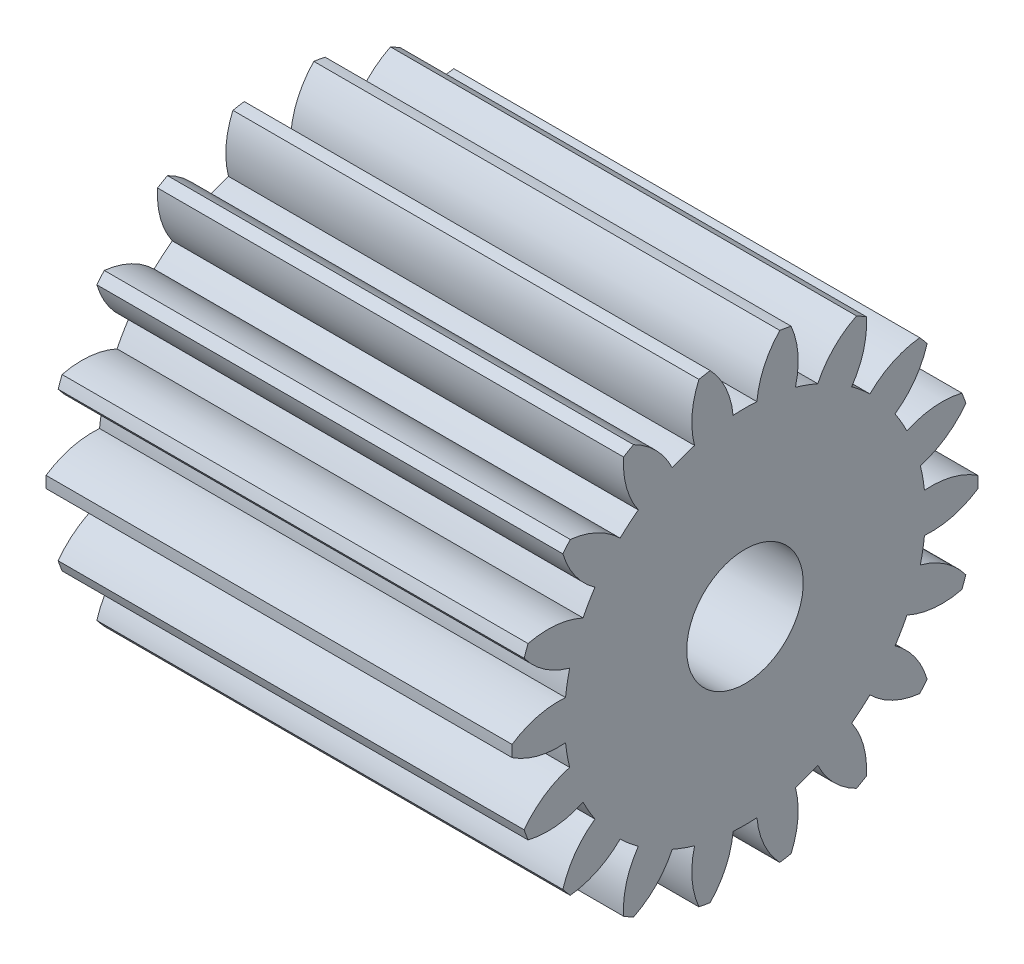
SolidWorks part; units mm, degrees
ref_plane "Plane1" through (0, 0, 0) normal (0, 0, 1) x (1, 0, 0)
ref_plane "Plane2" through (0, 0, 0) normal (0, 1, 0) x (1, 0, 0)
ref_plane "Plane3" through (0, 0, 0) normal (1, 0, 0) x (0, 0, -1)
sketch "HoldingSke" plane through (0, 0, 0) normal (0, 1, 0) x (1, 0, 0)
  line L0 (0, 0) -> (1.9021, -0.618)
  line L1 (-15, 0) -> (100, 0) construction
  line L2 (0, 0) -> (-2.1039, 2.3779)
  line L3 (0, 0) -> (-11.863, 4.5341)
  line L4 (0, 0) -> (8.2133, 2.6687)
  line L5 (0, 0) -> (-46.8476, -17.4728)
  line L6 (0, 0) -> (-8.2896, -5.593)
  line L7 (-2.1039, 2.3779) -> (8.6586, 51.2059)
  line L8 (-76.2, 54.61) -> (-76.1, 54.61)
  line L9 (-71.009, 38.7566) -> (-53.1078, 45.2721)
  line L10 (-76.2, 71.12) -> (104.1128, 71.12)
  line L11 (0, 0) -> (-10, 0)
  line L12 (-76.2, 101.6) -> (-76.181, 101.6)
  line L13 (24.9733, 27.94) -> (52.9518, 28.4284)
  line L14 (24.9733, 27.94) -> (24.9743, 27.94)
  line L15 (24.9733, 27.94) -> (100.4006, 29.5858)
  line L16 (-63.627, -0.5) -> (-12.827, -0.5)
  circle A0 centre (0, 0) radius 0.4
  circle A1 centre (0, 0) radius 3.874
  circle A2 centre (0, 0) radius 37.5
  circle A3 centre (0, 0) radius 1.25
  dimension "Num_teeth" = 18
  dimension "Pitch_radius" = 180.3128
  dimension "Width" = 10
  dimension "Thickness" = 10
sketch "BasProSke" plane through (0, 0, 0) normal (0, 1, 0) x (1, 0, 0)
  line L0 (-10, 0) -> (60, 0) construction
  line L1 (0, 0) -> (0, 5)
  line L2 (0, 0) -> (10, 0)
  line L3 (10, 0) -> (10, 5)
  line L4 (10, 5) -> (0, 5)
  dimension "Thickness" = 10
  dimension "Diameter" = 10
revolve "Base-Revolve" add sketch "BasProSke" angle 360 about L0
sketch "TooCutSke" plane through (0, 0, 0) normal (1, 0, 0) x (0, 0, -1)
  line L1 (0, 0) -> (0, 107) construction
  line L2 (0, 0) -> (-0.4254, 4.4798) construction
  line L3 (0, 0) -> (-1.5579, 8.835) construction
  line L4 (-0.4254, 4.4798) -> (-0.7789, 4.4175) construction
  arc A0 (0.2553, 3.8656) -> (-0.2553, 3.8656) centre (0, 0) ccw
  arc A1 (0.7686, 4.9663) -> (-0.7686, 4.9663) centre (0, 0) ccw
  circle A2 centre (0, 0) radius 4.5 construction
  circle A3 centre (0, 0) radius 4.2286 construction
  arc A4 (-0.2553, 3.8656) -> (-0.7686, 4.9663) centre (-2.0476, 3.6998) ccw
  arc A5 (0.7686, 4.9663) -> (0.2553, 3.8656) centre (2.0476, 3.6998) ccw
extrude "ToothCut" cut sketch "TooCutSke" along normal through all
fillet "Breaks" [suppressed] radius 0.01 tangent propagation no
fillet "RootFillets" [suppressed] radius 0.126
pattern_circular "TeethCuts" count 18 every 20 about axis through (-10, 0, 0) along (1, 0, 0) of "ToothCut", "RootFillets", "Breaks"
sketch "HubNeaOneSke" plane through (0, 0, 0) normal (-1, 0, 0) x (0, 0, 1)
  circle A0 centre (0, 0) radius 3.874
  dimension "Diameter" = 7.748
extrude "HubNearOne" [suppressed] add sketch "HubNeaOneSke" along normal blind 40.0001
sketch "HubNeaBotSke" plane through (0, 0, 0) normal (-1, 0, 0) x (0, 0, 1)
  circle A0 centre (0, 0) radius 3.874
  dimension "Diameter" = 7.748
extrude "HubNearBoth" [suppressed] add sketch "HubNeaBotSke" along normal blind 20
ref_plane "FarPln" through (10, 0, 0) normal (1, 0, 0) x (0, 0, -1)
sketch "HubFarSke" plane through (10, 0, 0) normal (1, 0, 0) x (0, 0, -1)
  circle A0 centre (0, 0) radius 3.874
  dimension "Diameter" = 7.748
extrude "HubFar" [suppressed] add sketch "HubFarSke" along normal blind 20
sketch "BorSke" plane through (0, 0, 0) normal (1, 0, 0) x (0, 0, -1)
  circle A0 centre (0, 0) radius 1.25
  dimension "Diameter" = 2.5
extrude "Bore" cut sketch "BorSke" along normal mid plane 100.0001
sketch "KeySke" plane through (0, 0, 0) normal (1, 0, 0) x (0, 0, -1)
  line L0 (-0.05, 0) -> (-0.05, 1.35)
  line L1 (-0.05, 1.35) -> (0.05, 1.35)
  line L2 (0.05, 1.35) -> (0.05, 0)
  line L3 (0, 0) -> (0, 34) construction
  line L4 (-0.05, 0) -> (0.05, 0)
  dimension "Width" = 0.1
extrude "Keyway" [suppressed] cut sketch "KeySke" along normal mid plane 100.0001
pattern_circular "Keyway2" [suppressed] count 2 every 90 about axis through (-10, 0, 0) along (1, 0, 0)
equation "' \"Module@HoldingSke\" = 6.35"
equation "' \"Num_teeth@HoldingSke\" = 12"
equation "' \"Ap@HoldingSke\" =  20"
equation "' \"Ap@HoldingSke\" = 20"
equation "' \"Width@HoldingSke\" = 0.5 * 25.4"
equation "' \"Hub_dia@HoldingSke\"= 1 * 25.4"
equation "' \"Hub_dia@HoldingSke\" = 1 * 25.4"
equation "' \"Overall_len@HoldingSke\" = 1.0 * 25.4"
equation "' \"Bore@HoldingSke\" = 0.75 * 25.4"
equation "' \"T_dim@HoldingSke\" = 0.1 * 25.4"
equation "' \"Width@KeySke\" = 0.25 * 25.4"
equation "' \"Show_teeth@HoldingSke\" = 13"
equation "' \"Backlash@HoldingSke\" = 0.009 * 25.4"
equation "' \"Addendum_fac@HoldingSke\" = 1.0"
equation "' \"Dedendum_fac@HoldingSke\" = 1.25"
equation "' \"Dedendum_add@HoldingSke\" = 0.00005 * 25.4"
equation "' \"Clearance_fac@HoldingSke\" = 0.25"
equation "\"Pitch@HoldingSke\" = 1 / \"Module@HoldingSke\""
equation "\"Overcut_dia@TooCutSke\" = (\"Num_teeth@HoldingSke\" + 2 * \"Addendum_fac@HoldingSke\") / \"Pitch@HoldingSke\" + 0.002 * 25.4"
equation "\"Pitch_dia@TooCutSke\" = \"Num_teeth@HoldingSke\" / \"Pitch@HoldingSke\""
equation "\"Base_dia@TooCutSke\" = \"Num_teeth@HoldingSke\" / \"Pitch@HoldingSke\" * cos((\"Ap@HoldingSke\"  * 3.14159265 / 180))"
equation "\"Root_dia@TooCutSke\" = (\"Num_teeth@HoldingSke\" + 2) / \"Pitch@HoldingSke\" - 2 * (\"Addendum_fac@HoldingSke\" + \"Dedendum_fac@HoldingSke\") / \"Pitch@HoldingSke\" - \"Dedendum_add@HoldingSke\" * 2"
equation "\"Half_ang@TooCutSke\" = 180 / \"Num_teeth@HoldingSke\""
equation "\"Half_CT@TooCutSke\" = \"Num_teeth@HoldingSke\" / \"Pitch@HoldingSke\" * sin((3.14159265 / 2 / \"Num_teeth@HoldingSke\")) / 2 - 7 * \"Backlash@HoldingSke\" / 4"
equation "\"Flank_rad@TooCutSke\" = \"Num_teeth@HoldingSke\" / \"Pitch@HoldingSke\" / 5"
equation "\"Radius@RootFillets\" = \"Clearance_fac@HoldingSke\" / \"Pitch@HoldingSke\" + \"Dedendum_add@HoldingSke\""
equation "\"Break_rad@Breaks\" = 0.02 / \"Pitch@HoldingSke\""
equation "\"Thickness@HoldingSke\" = \"Width@HoldingSke\""
equation "\"OAL@HoldingSke\" = \"Thickness@HoldingSke\""
equation "\"MHD@HoldingSke\" = (\"Num_teeth@HoldingSke\" + 2) / \"Pitch@HoldingSke\" - 2 * (\"Addendum_fac@HoldingSke\" + \"Dedendum_fac@HoldingSke\")  / \"Pitch@HoldingSke\" - \"Dedendum_add@HoldingSke\" * 2"
equation "\"MHD@HoldingSke\" = ((sgn( \"MHD@HoldingSke\" - \"Hub_dia@HoldingSke\" )-1)*( \"MHD@HoldingSke\" - \"Hub_dia@HoldingSke\" ))/-2+ \"Hub_dia@HoldingSke\""
equation "\"OAL@HoldingSke\" = ((sgn( \"OAL@HoldingSke\" - \"Overall_len@HoldingSke\" )+1)*( \"OAL@HoldingSke\" - \"Overall_len@HoldingSke\" ))/2 + \"Overall_len@HoldingSke\" + 0.000002 * 25.4"
equation "\"Num_teeth@TeethCuts\" = int( \"Show_teeth@HoldingSke\" ) + 1"
equation "\"Num_teeth@TeethCuts\" = ((sgn( \"Num_teeth@TeethCuts\" - \"Num_teeth@HoldingSke\" )-1)*( \"Num_teeth@TeethCuts\" - \"Num_teeth@HoldingSke\" ))/-2+ \"Num_teeth@HoldingSke\""
equation "\"Num_teeth@TeethCuts\" = ((sgn( \"Num_teeth@TeethCuts\" - 2.0)+1)*( \"Num_teeth@TeethCuts\" - 2.0))/2 +2.0"
equation "\"Angle@TeethCuts\" = 360.0 / \"Num_teeth@HoldingSke\""
equation "\"Diameter@BasProSke\" = (\"Num_teeth@HoldingSke\" + 2 * \"Addendum_fac@HoldingSke\") / \"Pitch@HoldingSke\""
equation "\"Thickness@BasProSke\"  = \"Thickness@HoldingSke\""
equation "' \"Fillet_rad@BasProSke\" =  \"Thickness@HoldingSke\" * 0.05"
equation "' \"Fillet_rad@BasProSke\" = \"Thickness@HoldingSke\" * 0.05"
equation "\"MHD@HoldingSke\" = ((sgn( \"MHD@HoldingSke\" - \"Root_dia@TooCutSke\" )-1)*( \"MHD@HoldingSke\" - \"Root_dia@TooCutSke\" ))/-2+ \"Root_dia@TooCutSke\""
equation "\"Diameter@HubNeaOneSke\" = \"MHD@HoldingSke\""
equation "\"Length@HubNearOne\" = \"OAL@HoldingSke\" - \"Thickness@BasProSke\""
equation "\"Diameter@HubNeaBotSke\" = \"MHD@HoldingSke\""
equation "\"Length@HubNearBoth\" = ( \"OAL@HoldingSke\" - \"Thickness@BasProSke\" ) / 2.0"
equation "\"Thickness@FarPln\" = \"Thickness@BasProSke\""
equation "\"Diameter@HubFarSke\" = \"MHD@HoldingSke\""
equation "\"Length@HubFar\" = ( \"OAL@HoldingSke\" - \"Thickness@BasProSke\" ) / 2.0"
equation "\"Diameter@BorSke\" = \"MBD@HoldingSke\""
equation "\"D1@Bore\" = \"OAL@HoldingSke\" * 2.0"
equation "\"D1@Keyway\" = \"OAL@HoldingSke\" * 2.0"
equation "\"Offset@KeySke\" = \"T_dim@HoldingSke\" + \"MBD@HoldingSke\" / 2.0"
